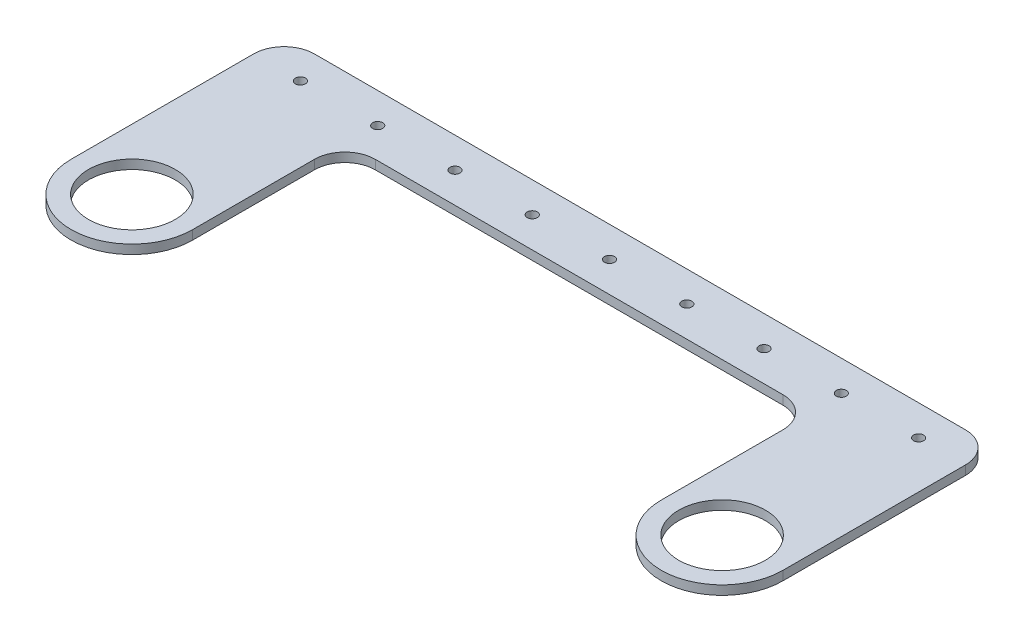
SolidWorks part; units mm, degrees
ref_plane "Front Plane" through (0, 0, 0) normal (0, 0, 1) x (1, 0, 0)
ref_plane "Top Plane" through (0, 0, 0) normal (0, 1, 0) x (1, 0, 0)
ref_plane "Right Plane" through (0, 0, 0) normal (1, 0, 0) x (0, 0, -1)
sketch "Sketch1" plane through (0, 0, 0) normal (0, 1, 0) x (1, 0, 0)
  line L0 (0, 0) -> (0, 18.1373) construction
  line L1 (-117, -10) -> (117, -10)
  line L2 (-117, -10) -> (-117, 10)
  line L3 (-117, 10) -> (117, 10)
  line L4 (117, -10) -> (117, 10)
  line L5 (-117, -10) -> (117, 10) construction
  line L6 (-117, 10) -> (117, -10) construction
  line L7 (-117, 10) -> (-77, 10)
  line L8 (-117, 10) -> (-117, -60)
  line L10 (-77, 10) -> (-77, -60)
  line L11 (117, 10) -> (117, -60)
  line L12 (77, 10) -> (77, -60)
  circle A0 centre (-97, -60) radius 20
  circle A1 centre (-97, -60) radius 14.26
  arc A2 (-57, -10) -> (-77, -30) centre (-57, -30) ccw
  circle A3 centre (97, -60) radius 14.26
  circle A4 centre (97, -60) radius 20
  arc A5 (57, -10) -> (77, -30) centre (57, -30) cw
  circle A6 centre (0, 0) radius 1.65
  circle A7 centre (25.4, 0) radius 1.65
  circle A8 centre (50.8, 0) radius 1.65
  circle A9 centre (76.2, 0) radius 1.65
  circle A10 centre (101.6, 0) radius 1.65
  circle A11 centre (-25.4, 0) radius 1.65
  circle A12 centre (-50.8, 0) radius 1.65
  circle A13 centre (-76.2, 0) radius 1.65
  circle A14 centre (-101.6, 0) radius 1.65
  point P0 (0, 0)
  dimension "D5" = 40
  dimension "D6" = 28.52
  dimension "D7" = 40
  dimension "D3" = 3.3
  dimension "D1" = 20
  dimension "D2" = 234
  dimension "D4" = 40
  dimension "D8" = 5
  dimension "D9" = 5
extrude "Boss-Extrude1" add sketch "Sketch1" along normal blind 3 contours A0 L10 L1 L8 | A0 A1 | L10 L3 L2 L1 | L12 L3 L10 L1 | L3 L12 L1 L4 | L12 A4 L11 L1 | A4 A3 region at (-67, 0, 8.4471) region at (-97, 0, 27.4366) region at (-96.9936, 0, 0) region at (96.9936, 0, 0) region at (97, 0, 27.4366) region at (-97, 0, 79.4343) region at (97, 0, 40.5657)
fillet "Fillet1" radius 10 4 edges at (117, 1.5, -10) (-117, 1.5, -10) (77, 1.5, 10) (-77, 1.5, 10)
